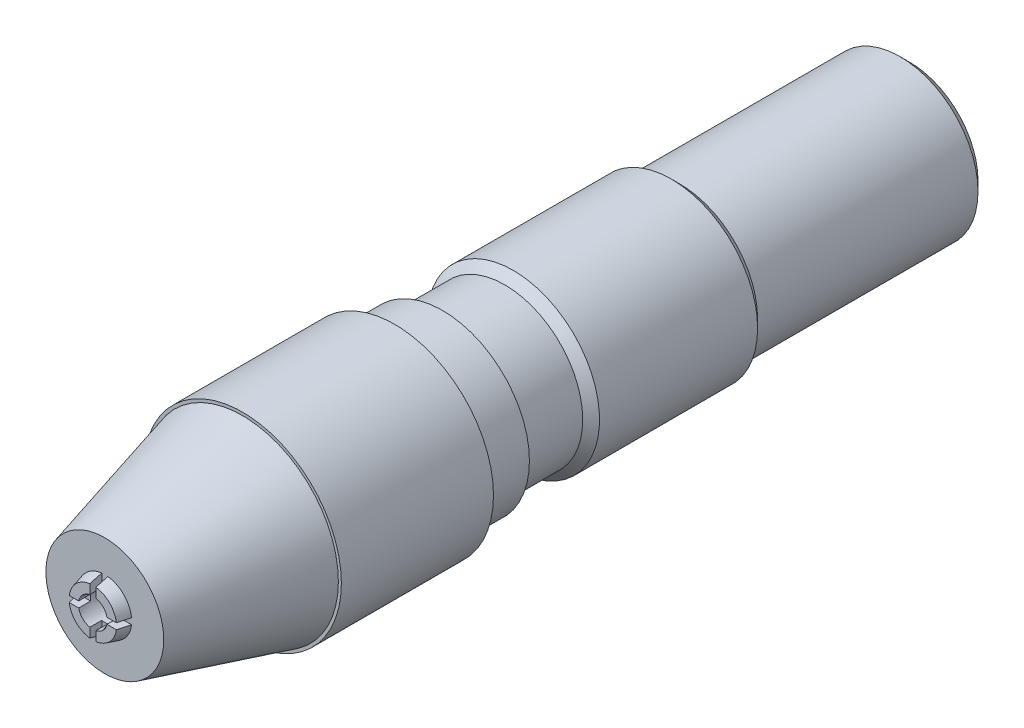
SolidWorks part; units mm, degrees
material "Plain Carbon Steel"
ref_plane "Front Plane" through (0, 0, 0) normal (0, 0, 1) x (1, 0, 0)
ref_plane "Top Plane" through (0, 0, 0) normal (0, 1, 0) x (1, 0, 0)
ref_plane "Right Plane" through (0, 0, 0) normal (1, 0, 0) x (0, 0, -1)
sketch "Sketch1" plane through (0, 0, 0) normal (0, 0, 1) x (1, 0, 0)
  circle A1 centre (0, 0) radius 3.25
  dimension "D2" = 6.5
extrude "Extrude1" add sketch "Sketch1" along normal blind 10
sketch "Sketch2" plane through (0, 0, 10) normal (0, 0, 1) x (1, 0, 0)
  circle A0 centre (0, 0) radius 3.6
  dimension "D1" = 7.2
extrude "Extrude2" add sketch "Sketch2" along normal blind 6.5
sketch "Sketch3" plane through (0, 0, 16.5) normal (0, 0, 1) x (1, 0, 0)
  circle A0 centre (0, 0) radius 3.25
  dimension "D1" = 6.5
extrude "Extrude3" add sketch "Sketch3" along normal blind 3
sketch "Sketch4" plane through (0, 0, 19.5) normal (0, 0, 1) x (1, 0, 0)
  circle A0 centre (0, 0) radius 3.625
  dimension "D1" = 7.25
extrude "Extrude4" add sketch "Sketch4" along normal blind 2
sketch "Sketch5" plane through (0, 0, 21.5) normal (0, 0, 1) x (1, 0, 0)
  circle A0 centre (0, 0) radius 4.125
  dimension "D1" = 8.25
extrude "Extrude5" add sketch "Sketch5" along normal blind 6.35
sketch "Sketch6" plane through (0, 0, 27.85) normal (0, 0, 1) x (1, 0, 0)
  circle A0 centre (0, 0) radius 4
  dimension "D1" = 8
extrude "Extrude6" add sketch "Sketch6" along normal blind 5.75 draft 15
sketch "Sketch7" plane through (0, 0, 33.6) normal (0, 0, 1) x (1, 0, 0)
  circle A0 centre (0, 0) radius 1.125
  dimension "D1" = 2.25
extrude "Extrude7" add sketch "Sketch7" along normal blind 0.5 draft 15
sketch "Sketch8" plane through (0, 0, 34.1) normal (0, 0, 1) x (1, 0, 0)
  line L0 (0, 2.185) -> (0, -2.499)
extrude "Cut-Extrude-Thin2" cut sketch "Sketch8" against normal up to surface (0.5 mm away) thin up to face at (2.4593, 0, 33.6) thin type mid plane wall 0.254
sketch "Sketch9" plane through (0, 0, 34.1) normal (0, 0, 1) x (1, 0, 0)
  line L0 (-2.0804, 0) -> (1.125, 0)
  arc A0 (0.127, -1.1178) -> (0.127, 1.1178) centre (0, 0) ccw construction
extrude "Cut-Extrude-Thin3" cut sketch "Sketch9" against normal up to surface (0.5 mm away) thin up to face at (0.626, 0, 33.6) thin type mid plane wall 0.254
chamfer "Chamfer1" distance 0.4 angle 45 3 edges at (3.25, 0, 16.5) (3.25, 0, 10) (3.25, 0, 0)
sketch "Sketch10" plane through (0, 0, 0) normal (0, 0, -1) x (-1, 0, 0)
  circle A0 centre (0, 0) radius 0.9
  dimension "D1" = 1.8
extrude "Cut-Extrude1" cut sketch "Sketch10" against normal up to surface (34.1 mm away) draft 0.5 up to face at (-0.4609, -0.4609, 34.1)
